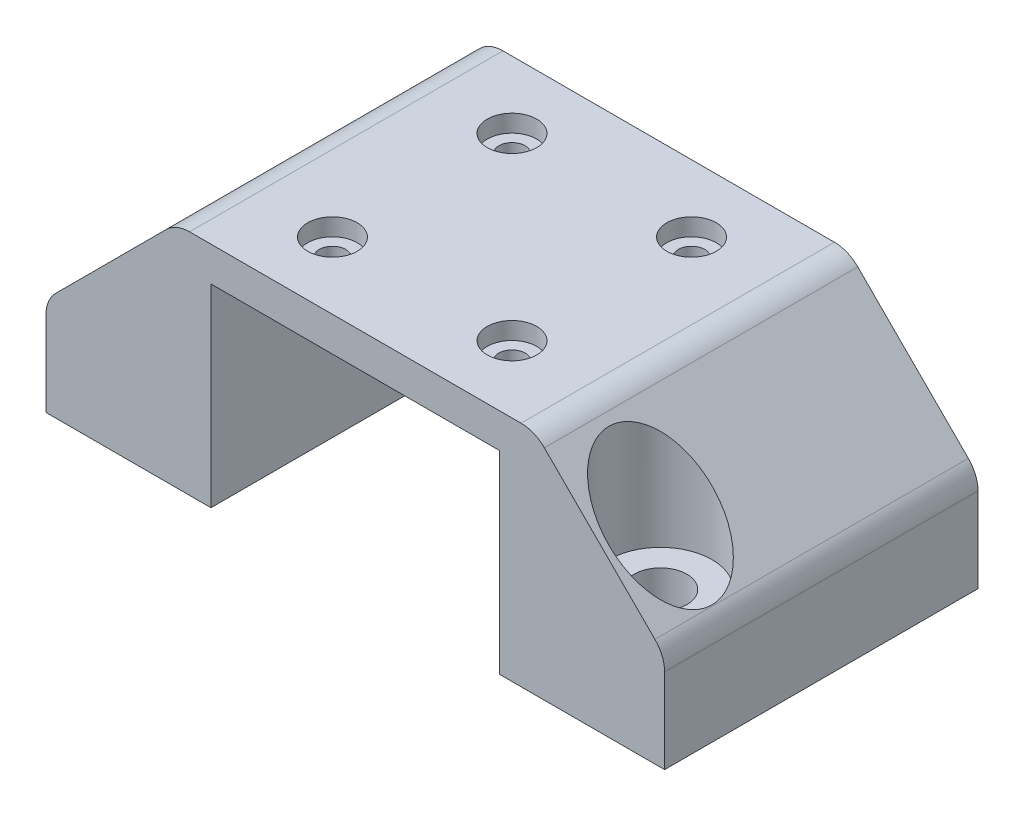
SolidWorks part; units mm, degrees
ref_plane "Front Plane" through (0, 0, 0) normal (0, 0, 1) x (1, 0, 0)
ref_plane "Top Plane" through (0, 0, 0) normal (0, 1, 0) x (1, 0, 0)
ref_plane "Right Plane" through (0, 0, 0) normal (1, 0, 0) x (0, 0, -1)
sketch "Sketch1" plane through (0, 0, 0) normal (0, 0, 1) x (1, 0, 0)
  line L0 (0, -12.67) -> (0, 30.502) construction
  line L1 (-11.1125, 0) -> (-11.1125, 14.9225)
  line L2 (-11.1125, 0) -> (-23.8125, 0)
  line L3 (-11.1125, 14.9225) -> (11.1125, 14.9225)
  line L4 (-23.8125, 17.5746) -> (23.8125, 17.5746)
  line L5 (-23.8125, 0) -> (-23.8125, 17.5746)
  line L6 (11.1125, 0) -> (23.8125, 0)
  line L7 (23.8125, 0) -> (23.8125, 17.5746)
  line L8 (11.1125, 0) -> (11.1125, 14.9225)
  point P9 (0, 17.5746)
  point P13 (0, 14.9225)
  dimension "D1" = 12.7
  dimension "D2" = 11.1125
  dimension "D3" = 14.9225
  dimension "D4" = 17.5746
extrude "Boss-Extrude1" add sketch "Sketch1" along normal blind 24.13
chamfer "Chamfer1" distance 10 angle 45 2 edges at (23.8125, 17.5746, 12.065) (-23.8125, 17.5746, 12.065)
fillet "Fillet1" radius 2.54 2 edges at (13.8125, 17.5746, 12.065) (-13.8125, 17.5746, 12.065)
fillet "Fillet2" radius 2.54 2 edges at (23.8125, 7.5746, 12.065) (-23.8125, 7.5746, 12.065)
sketch "Sketch2" plane through (0, 0, 0) normal (0, -1, 0) x (1, 0, 0)
  line L0 (0, -12.2519) -> (0, 31.6273) construction
  line L1 (-35.4754, 12.065) -> (35.4754, 12.065) construction
  line L2 (-11.1125, 0) -> (11.1125, 0) construction
  circle A0 centre (-19.05, 19.685) radius 2.032
  circle A1 centre (19.05, 19.685) radius 2.032
  dimension "D1" = 4.064
  dimension "D2" = 7.62
  dimension "D3" = 12.065
  dimension "D4" = 19.05
extrude "Cut-Extrude1" cut sketch "Sketch2" against normal blind 10.16
sketch "Sketch3" plane through (0, 17.5746, 0) normal (0, 1, 0) x (1, 0, 0)
  line L0 (0, 9.1955) -> (0, -28.8887) construction
  line L1 (-14.5564, -12.065) -> (14.5564, -12.065) construction
  line L2 (-14.5564, -24.13) -> (-14.5564, 0) construction
  line L3 (14.5564, 0) -> (14.5564, -24.13) construction
  circle A0 centre (-6.9113, -5.1537) radius 1.016
  circle A1 centre (6.9113, -5.1537) radius 1.016
  circle A2 centre (6.9113, -18.9763) radius 1.016
  circle A3 centre (-6.9113, -18.9763) radius 1.016
  dimension "D3" = 2.032
  dimension "D1" = 6.9113
  dimension "D2" = 6.9113
extrude "Cut-Extrude2" cut sketch "Sketch3" against normal through all
sketch "Sketch4" plane through (0, 17.5746, 0) normal (0, 1, 0) x (1, 0, 0)
  line L0 (0, 10.8653) -> (0, -31.1365) construction
  line L1 (-14.5564, -12.065) -> (14.5564, -12.065) construction
  line L2 (-14.5564, -24.13) -> (-14.5564, 0) construction
  line L3 (14.5564, 0) -> (14.5564, -24.13) construction
  circle A0 centre (-6.9113, -5.1537) radius 1.905
  circle A1 centre (6.9113, -5.1537) radius 1.905
  circle A2 centre (6.9113, -18.9763) radius 1.905
  circle A3 centre (-6.9113, -18.9763) radius 1.905
  dimension "D1" = 3.81
extrude "Cut-Extrude3" cut sketch "Sketch4" against normal blind 1.3335
sketch "Sketch5" plane through (0, 0, 0) normal (0, -1, 0) x (1, 0, 0)
  line L0 (0, 26.4248) -> (0, -11.0183) construction
  line L1 (-23.8125, 12.065) -> (23.8125, 12.065) construction
  line L2 (-23.8125, 24.13) -> (-23.8125, 0) construction
  line L3 (23.8125, 24.13) -> (23.8125, 0) construction
  circle A0 centre (-19.05, 4.445) radius 2.032
  circle A2 centre (19.05, 4.445) radius 2.032
  dimension "D3" = 4.064
  dimension "D1" = 7.62
  dimension "D2" = 19.05
extrude "Cut-Extrude4" cut sketch "Sketch5" against normal blind 10.16
sketch "Sketch7" plane through (0, 17.5746, 0) normal (0, 1, 0) x (1, 0, 0)
  line L0 (0, 10.3263) -> (0, -35.1994) construction
  line L1 (-23.8125, -12.065) -> (23.8125, -12.065) construction
  line L2 (-23.8125, -24.13) -> (-23.8125, 0) construction
  line L3 (23.8125, 0) -> (23.8125, -24.13) construction
  circle A2 centre (19.05, -19.685) radius 3.9688
  circle A3 centre (-19.05, -19.685) radius 3.9688
extrude "Cut-Extrude5" cut sketch "Sketch7" against normal blind 10.16
